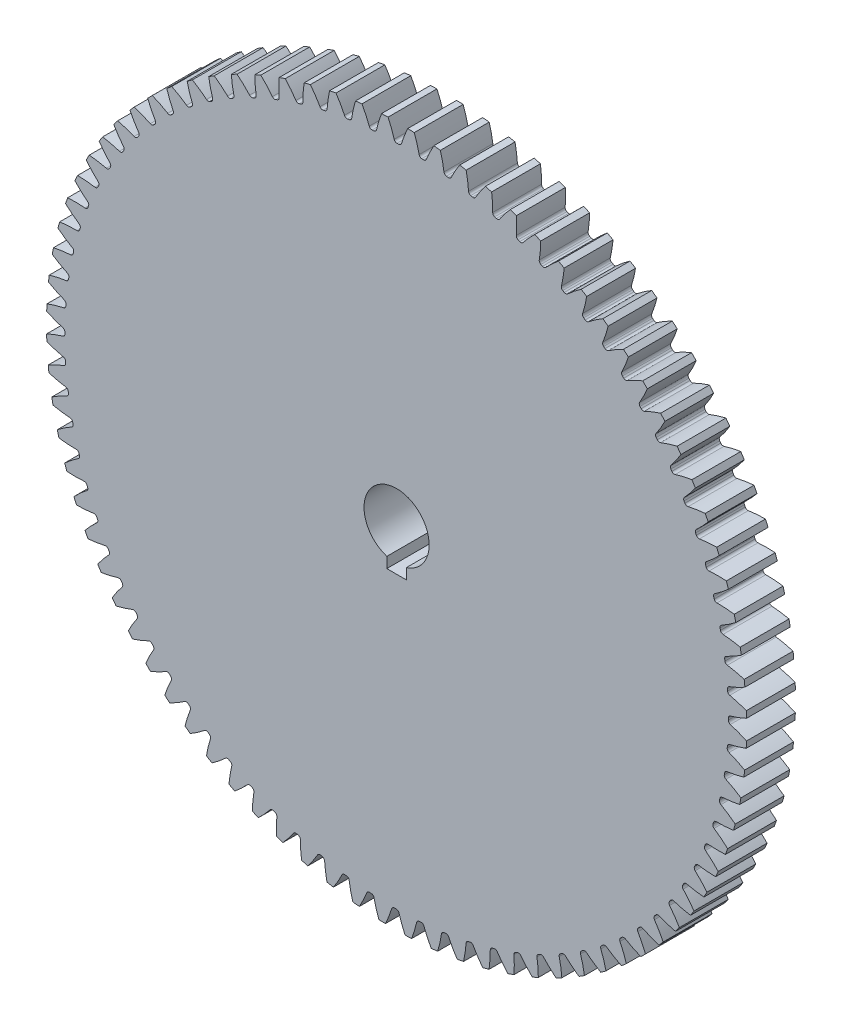
SolidWorks part; units mm, degrees
ref_plane "前视基准面" through (0, 0, 0) normal (0, 0, 1) x (1, 0, 0)
ref_plane "上视基准面" through (0, 0, 0) normal (0, 1, 0) x (1, 0, 0)
ref_plane "右视基准面" through (0, 0, 0) normal (1, 0, 0) x (0, 0, -1)
sketch "草图1" plane through (0, 0, 0) normal (0, 0, 1) x (1, 0, 0)
  circle A0 centre (0, 0) radius 107.5
  dimension "D1" = 215
extrude "凸台-拉伸1" add sketch "草图1" along normal mid plane 15
sketch "草图4" plane through (0, 0, 0) normal (0, 0, 1) x (1, 0, 0)
  line L1 (0, 0) -> (139.5362, -0.5296) construction
  arc A1 (104.9883, 1.5649) -> (104.9992, -0.3985) centre (0, 0) cw construction
  arc A3 (136.3364, 29.7156) -> (136.1069, -30.7497) centre (0, 0) cw
  circle A4 centre (0, 0) radius 101.875
  spline S0 degree 4 poles (98.6649, -0.749) (98.7378, -0.7511) (98.9422, -0.7618) (99.3275, -0.8007) (99.9535, -0.8911) (100.746, -1.0451) (101.7625, -1.2888) (102.948, -1.6326) (104.2362, -2.0696) (105.9654, -2.7421) (107.9977, -3.6572) (110.2563, -4.8328) (112.7613, -6.3279) (115.1841, -7.9526) (117.5254, -9.6923) (119.8265, -11.5719) (122.0444, -13.5487) (123.9133, -15.3557) (125.4644, -16.955) (126.7235, -18.3193) (127.7106, -19.4288) (128.9198, -20.8376) (130.0957, -22.274) (131.2393, -23.7371) (132.572, -25.5214) (133.5433, -26.8824) (134.3826, -28.1051) (135.1032, -29.1908) (135.5001, -29.7983) (136.0167, -30.6043) (136.424, -31.2524) (137.1472, -32.4236) (137.6609, -33.2943) (138.2173, -34.2393) (138.4662, -34.6853) (138.6429, -34.9933) knots 0 0 0 0 0 0.005377 0.015084 0.028532 0.04661 0.064855 0.092111 0.119476 0.146842 0.201575 0.256307 0.307035 0.361767 0.4165 0.471232 0.525964 0.580697 0.608063 0.635429 0.662795 0.690161 0.744894 0.77226 0.799626 0.854358 0.868042 0.881725 0.895408 0.909091 0.931818 0.954545 0.977273 1 1 1 1 1 construction
  spline S1 degree 4 poles (98.6649, -0.749) (98.7378, -0.7511) (98.9422, -0.7618) (99.3275, -0.8007) (99.9535, -0.8911) (100.746, -1.0451) (101.7625, -1.2888) (102.948, -1.6326) (104.2362, -2.0696) (105.9654, -2.7421) (107.9977, -3.6572) (110.2563, -4.8328) (112.7613, -6.3279) (115.1841, -7.9526) (117.5254, -9.6923) (119.8265, -11.5719) (122.0444, -13.5487) (123.9133, -15.3557) (125.4644, -16.955) (126.7235, -18.3193) (127.7106, -19.4288) (128.9198, -20.8376) (130.0957, -22.274) (131.2393, -23.7371) (132.572, -25.5214) (133.5433, -26.8824) (134.3826, -28.1051) (135.1032, -29.1908) (135.5001, -29.7983) (135.8326, -30.3171) (136.0168, -30.607) (136.1069, -30.7497) knots 0 0 0 0 0 0.005377 0.015084 0.028532 0.04661 0.064855 0.092111 0.119476 0.146842 0.201575 0.256307 0.307035 0.361767 0.4165 0.471232 0.525964 0.580697 0.608063 0.635429 0.662795 0.690161 0.744894 0.77226 0.799626 0.854358 0.868042 0.881725 0.895408 0.909091 0.909091 0.909091 0.909091 0.909091
  spline S2 degree 4 poles (98.6677, 0) (98.7407, 0.0015) (98.9451, 0.0107) (99.3307, 0.0467) (99.9574, 0.1323) (100.751, 0.2803) (101.7693, 0.5163) (102.9574, 0.8511) (104.2489, 1.2782) (105.9831, 1.9377) (108.0223, 2.8373) (110.2898, 3.9957) (112.8061, 5.4718) (115.2411, 7.078) (117.5956, 8.7998) (119.9109, 10.662) (122.1438, 12.6218) (124.0263, 14.4146) (125.5895, 16.002) (126.8589, 17.3568) (127.8544, 18.4588) (129.0742, 19.8584) (130.2611, 21.2858) (131.4157, 22.7401) (132.7619, 24.5143) (133.7435, 25.8679) (134.5921, 27.0842) (135.3209, 28.1644) (135.7224, 28.7688) (136.2451, 29.5709) (136.6573, 30.2159) (137.3894, 31.3816) (137.9097, 32.2483) (138.4732, 33.189) (138.7255, 33.6332) (138.9045, 33.9398) knots 0 0 0 0 0 0.005377 0.015084 0.028532 0.04661 0.064855 0.092111 0.119476 0.146842 0.201575 0.256307 0.307035 0.361767 0.4165 0.471232 0.525964 0.580697 0.608063 0.635429 0.662795 0.690161 0.744894 0.77226 0.799626 0.854358 0.868042 0.881725 0.895408 0.909091 0.931818 0.954545 0.977273 1 1 1 1 1 construction
  spline S3 degree 4 poles (98.6677, 0) (98.7407, 0.0015) (98.9451, 0.0107) (99.3307, 0.0467) (99.9574, 0.1323) (100.751, 0.2803) (101.7693, 0.5163) (102.9574, 0.8511) (104.2489, 1.2782) (105.9831, 1.9377) (108.0223, 2.8373) (110.2898, 3.9957) (112.8061, 5.4718) (115.2411, 7.078) (117.5956, 8.7998) (119.9109, 10.662) (122.1438, 12.6218) (124.0263, 14.4146) (125.5895, 16.002) (126.8589, 17.3568) (127.8544, 18.4588) (129.0742, 19.8584) (130.2611, 21.2858) (131.4157, 22.7401) (132.7619, 24.5143) (133.7435, 25.8679) (134.5921, 27.0842) (135.3209, 28.1644) (135.7224, 28.7688) (136.0589, 29.2851) (136.2452, 29.5736) (136.3364, 29.7156) knots 0 0 0 0 0 0.005377 0.015084 0.028532 0.04661 0.064855 0.092111 0.119476 0.146842 0.201575 0.256307 0.307035 0.361767 0.4165 0.471232 0.525964 0.580697 0.608063 0.635429 0.662795 0.690161 0.744894 0.77226 0.799626 0.854358 0.868042 0.881725 0.895408 0.909091 0.909091 0.909091 0.909091 0.909091
  dimension "D1" = 105
  dimension "D3" = 203.75
  dimension "D2" = 1.9635
ref_plane "基准面2" through (0, 0, 0) normal (-0.0038, -1, 0) x (1, -0.0038, 0)
extrude "切除-拉伸1" cut sketch "草图4" against normal through all both and the other way through all contours S3 A4 S1 A3 region at (127.4797, -0.4839, 0)
fillet "圆角1" radius 0.875 2 edges at (101.8663, -1.3282, 0) (101.8735, 0.5548, 0)
pattern_circular "阵列(圆周)1" count 84 over 360 about axis through (0, 0, 7.5) along (0, 0, -1) of "切除-拉伸1", "圆角1" reverse direction yes
sketch "草图5" plane through (0, 0, 0) normal (0, 0, 1) x (1, 0, 0)
  line L1 (-3, 0) -> (3, 0)
  line L2 (-3, 0) -> (-3, -12.8)
  line L3 (-3, -12.8) -> (3, -12.8)
  line L4 (3, 0) -> (3, -12.8)
  line L5 (-3, 0) -> (3, -12.8) construction
  line L6 (-3, -12.8) -> (3, 0) construction
  circle A0 centre (0, 0) radius 10
  point P3 (0, -6.4)
  dimension "D1" = 20
  dimension "D2" = 22.8
  dimension "D3" = 6
extrude "切除-拉伸2" cut sketch "草图5" against normal through all both and the other way through all contours A0 L2 L3 L4 | A0 region at (0, -11.3208, 0)
sketch "草图6" plane through (0, 0, 7.5) normal (0, 0, 1) x (1, 0, 0)
  circle A0 centre (0, 0) radius 105 construction
  dimension "D1" = 210
equation "\"D1@草图1\" = \"da\""
equation "\"D1@凸台-拉伸1\"=\"b\""
equation "\"b\"= 15'齿轮宽度"
equation "\"m\"= 2.5'模数"
equation "\"z\"= 84'齿数"
equation "\"x\"= 0'变位系数"
equation "\"pz\"= pi * \"m\"'导程"
equation "\"ha*\"= 1'齿顶高系数"
equation "\"c*\"= 0.25'顶隙系数"
equation "\"d2\"= \"m\" * \"z\"'分度圆"
equation "\"alfa\"= 20'压力角"
equation "\"db\"= \"d2\" * cos ( \"alfa\" )'基圆"
equation "\"df\"= \"d2\" - 2 * ( \"ha*\" + \"c*\" - \"x\" ) * \"m\"'齿根圆"
equation "\"D1@草图4\"=\"d2\"/2"
equation "\"D2@草图4\"=\"pz\"/4"
equation "\"D1@阵列(圆周)1\"=\"z\""
equation "\"D3@草图4\"=\"df\""
equation "\"da\"= \"d2\" + 2 * ( \"ha*\" + \"x\" ) * \"m\"'齿顶圆"
equation "\"c\"= \"m\" * 0.35'齿根圆角"
equation "\"dh\"= 20'内孔直径"
equation "\"h\"= 22.8'槽深"
equation "\"D1@草图5\"=\"dh\""
equation "\"D2@草图5\"=\"h\""
equation "\"k\"= 6'槽宽"
equation "\"D1@圆角1\"=\"c\""
